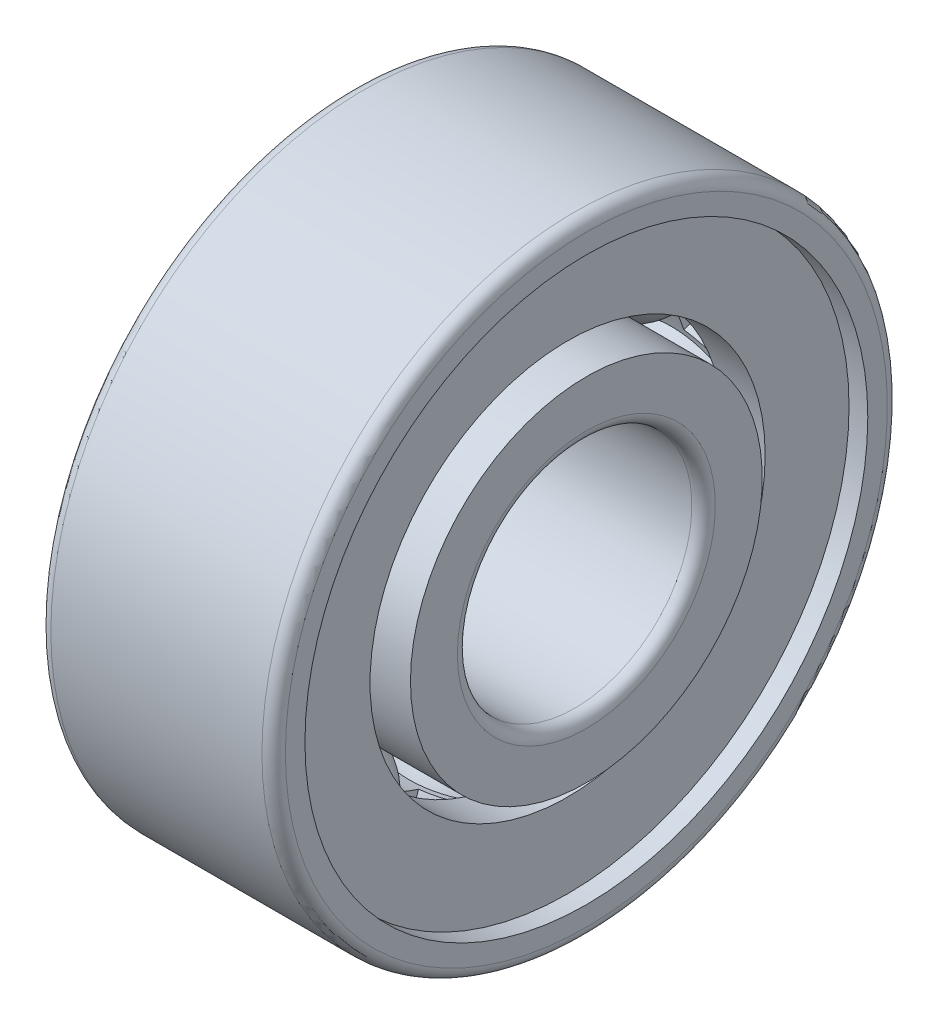
SolidWorks part; units mm, degrees
revolve "凸台-旋转2" add sketch "草图6" angle 360 about L4
sketch "草图6" plane through (0, 0, 0) normal (0, 0, 1) x (1, 0, 0)
  line L0 (0, 0) -> (5.5439, 0) construction
  line L1 (-12.4206, 0) -> (9.8128, 0) construction
  line L2 (0, 0) -> (0, 11.4011) construction
  line L3 (-5.5681, 2.925) -> (6.1049, 2.925) construction
  line L4 (-5.5681, 2.925) -> (6.1049, 2.925) construction
  line L5 (-0.84, 2.925) -> (0.84, 2.925)
  arc A0 (-0.84, 2.925) -> (0.84, 2.925) centre (0, 2.925) ccw
  dimension "Dw" = 1.68
revolve "基体-旋转" add sketch "草图2" angle 360 about L0
sketch "草图2" plane through (0, 0, 0) normal (0, 0, 1) x (1, 0, 0)
  line L0 (-12.4206, 0) -> (9.8128, 0) construction
  line L1 (0, 0) -> (0, 37.3563) construction
  line L2 (-5.5681, 2.925) -> (6.1049, 2.925) construction
  line L3 (-0.1848, 3.156) -> (0.1848, 3.156)
  line L4 (-0.1848, 3.156) -> (-0.1848, 2.694)
  line L5 (-0.1848, 2.694) -> (0.1848, 2.694)
  line L6 (0.1848, 3.156) -> (0.1848, 2.694)
  dimension "D1" = 0.3696
  dimension "D2" = 0.1848
  dimension "D3" = 0.462
  dimension "D4" = 0.231
  dimension "D5" = 2.925
revolve "凸台-旋转1" add sketch "草图3" angle 360 about L1
sketch "草图3" plane through (0, 0, 0) normal (0, 0, 1) x (1, 0, 0)
  line L0 (-5.5681, 2.925) -> (6.1049, 2.925) construction
  line L1 (-5.5681, 2.925) -> (6.1049, 2.925) construction
  line L2 (-12.4206, 0) -> (9.8128, 0) construction
  line L3 (-12.4206, 0) -> (9.8128, 0) construction
  line L4 (0, 0) -> (0, 37.3563) construction
  line L5 (0, 0) -> (0, 37.3563) construction
  line L6 (-0.924, 2.925) -> (0.924, 2.925)
  arc A0 (-0.924, 2.925) -> (0.924, 2.925) centre (0, 2.925) ccw
  dimension "Dwww" = 1.848
  dimension "D2" = 0.924
pattern_circular "阵列(圆周)1" count 8 over 360 about axis through (-12.4206, 0, 0) along (1, 0, 0) of "凸台-旋转1"
revolve "凸台-旋转3" add sketch "草图7" angle 360 about L0
sketch "草图7" plane through (0, 0, 0) normal (0, 0, 1) x (1, 0, 0)
  line L0 (0, 0) -> (6.6488, 0) construction
  line L1 (0, 0) -> (0, 16.8954) construction
  line L2 (-1.35, 4) -> (1.35, 4)
  line L3 (-1.5, 3.85) -> (-1.5, 3.6)
  line L4 (-1.5, 3.6) -> (-0.483, 3.6)
  line L5 (1.5, 3.85) -> (1.5, 3.6)
  line L6 (0.483, 3.6) -> (0.7248, 3.6)
  line L7 (1.26, 3.6) -> (1.5, 3.6)
  line L8 (0.7248, 3.4) -> (1.26, 3.4)
  line L9 (0.7248, 3.4) -> (0.7248, 3.6)
  line L11 (1.26, 3.4) -> (1.26, 3.6)
  arc A0 (-1.35, 4) -> (-1.5, 3.85) centre (-1.35, 3.85) ccw
  arc A1 (1.35, 4) -> (1.5, 3.85) centre (1.35, 3.85) cw
  arc A2 (0.8076, 3.156) -> (-0.8076, 3.156) centre (0, 2.925) ccw construction
  arc A3 (0.5, 3.6) -> (0, 3.765) centre (0, 2.925) ccw construction
  arc A4 (0.483, 3.6) -> (-0.483, 3.6) centre (0, 2.925) ccw
  point P10 (-1.5, 4)
  point P13 (1.5, 4)
  dimension "D3" = 1.5
  dimension "D4" = 0.5352
  dimension "D5" = 6.8
  dimension "D6" = 0.24
  dimension "B" = 3
ref_plane "基准面1" through (0, 0, 0) normal (0, 0, 1) x (1, 0, 0)
ref_plane "基准面2" through (0, 0, 0) normal (0, 1, 0) x (1, 0, 0)
ref_plane "基准面3" through (0, 0, 0) normal (1, 0, 0) x (0, 0, -1)
sketch "尺寸草图" plane through (0, 0, 0) normal (0, 0, 1) x (1, 0, 0)
  point P0 (0, -75.4307)
  point P1 (1.68, -75.4307)
  point P2 (0, 50.7088)
  point P3 (3, 50.7088)
  point P4 (8, 50.7088)
  point P5 (3, 50.7088)
  point P6 (0, -10.9899)
  point P7 (4.5, -10.9899)
  point P8 (6.8, -10.9899)
  point P9 (0.15, -10.9899)
  point P10 (8, -75.4307)
  dimension "B" = 3
sketch "草图4" plane through (0, 0, 0) normal (0, 0, 1) x (1, 0, 0)
  line L0 (0, 0) -> (8.1272, 0) construction
  line L1 (-12.4206, 0) -> (9.8128, 0) construction
  line L3 (-0.1848, 3.156) -> (0.1848, 3.156) construction
  line L4 (-0.924, 4.08) -> (0.924, 4.08)
  line L5 (-0.924, 4.08) -> (-0.924, 3.156)
  line L6 (-0.924, 3.156) -> (0.924, 3.156)
  line L7 (0.924, 4.08) -> (0.924, 3.156)
revolve "切除-旋转1" cut sketch "草图4" angle 360 about L0
sketch "草图5" plane through (0, 0, 0) normal (0, 0, 1) x (1, 0, 0)
  line L0 (0, 0) -> (8.2665, 0) construction
  line L1 (-12.4206, 0) -> (9.8128, 0) construction
  line L2 (-0.1848, 2.694) -> (0.1848, 2.694) construction
  line L3 (-0.924, 2.694) -> (0.924, 2.694)
  line L4 (-0.924, 2.694) -> (-0.924, 1.77)
  line L5 (-0.924, 1.77) -> (0.924, 1.77)
  line L6 (0.924, 2.694) -> (0.924, 1.77)
revolve "切除-旋转2" cut sketch "草图5" angle 360 about L0
pattern_circular "阵列(圆周)2" count 8 over 360 about axis through (-12.4206, 0, 0) along (1, 0, 0) of "凸台-旋转2"
sketch "草图8" plane through (0, 0, 0) normal (0, 0, 1) x (1, 0, 0)
  line L0 (-12.4206, 0) -> (9.8128, 0) construction
  line L1 (-12.4206, 0) -> (9.8128, 0) construction
  line L2 (1.5, 3.85) -> (1.5, 3.6) construction
  line L3 (-1.5, 2.25) -> (-0.483, 2.25)
  line L4 (-1.5, 2.25) -> (-1.5, 1.65)
  line L5 (-1.35, 1.5) -> (1.35, 1.5)
  line L6 (1.5, 2.25) -> (1.5, 1.65)
  line L7 (-1.5, 3.85) -> (-1.5, 3.6) construction
  line L8 (0.483, 2.25) -> (1.5, 2.25)
  arc A0 (-1.5, 1.65) -> (-1.35, 1.5) centre (-1.35, 1.65) ccw
  arc A1 (1.35, 1.5) -> (1.5, 1.65) centre (1.35, 1.65) ccw
  arc A2 (-0.8076, 2.694) -> (0.8076, 2.694) centre (0, 2.925) ccw construction
  arc A3 (-0.8076, 2.694) -> (0.8076, 2.694) centre (0, 2.925) ccw construction
  arc A4 (-0.483, 2.25) -> (0.483, 2.25) centre (0, 2.925) ccw
  dimension "D1" = 0.15
  dimension "DD" = 3
  dimension "D2" = 0.01
revolve "凸台-旋转4" add sketch "草图8" angle 360 about L1
sketch "草图10" plane through (0, 0, 0) normal (0, 0, 1) x (1, 0, 0)
  line L0 (0.7248, 3.6) -> (0.7248, -3.6) construction
  line L1 (1.26, 3.4) -> (0.7248, 3.4)
  line L2 (1.26, 3.4) -> (1.26, 2.5272)
  line L3 (1.26, 2.5272) -> (0.7248, 2.5272)
  line L4 (0.7248, 3.4) -> (0.7248, 2.5272)
  line L5 (0.483, 2.25) -> (1.5, 2.25) construction
  line L6 (0, 0) -> (-5.3515, 0) construction
  line L7 (-12.4206, 0) -> (9.8128, 0) construction
  dimension "D1" = 0.2772
revolve "凸台-旋转5" add sketch "草图10" angle 360 about L6
sketch "草图11" plane through (0, 0, 0) normal (1, 0, 0) x (0, 0, -1)
  circle A0 centre (0, 0) radius 4
  circle A1 centre (0, 0) radius 4 construction
extrude "切除-拉伸1" cut sketch "草图11" against normal blind 10
mirror "镜向所有1" about plane through (0, 0, 0) normal (1, 0, 0) of bodies 109
equation "\"D5@草图7\" = \"防尘圈径D3@尺寸草图\""
equation "\"Z@阵列(圆周)1\"=\"球数Z@尺寸草图\" "
equation "\"Dw@草图6\"=\"球径DW@尺寸草图\""
equation "\"DD@草图8\"=\"d@尺寸草图\""
equation "\"D@草图7\"=\"DD@尺寸草图\""
equation "\"B@草图7\"=\"B@尺寸草图\" "
equation "\"DD2@草图8\"=\"内圈外径DD2@尺寸草图\""
equation "\"R@草图7\"=\"r@尺寸草图\""
equation "\"D3@草图2\" = 0.25*\"Dwww@草图3\""
equation "\"D4@草图2\" = \"D3@草图2\"/2"
equation "\"Dwww@草图3\" = 1.1*\"Dw@草图6\""
equation "\"D2@草图3\" = 0.5*\"Dwww@草图3\""
equation "\"D1@草图2\" = 0.2*\"Dwww@草图3\""
equation "\"D2@草图2\" = 0.5*\"D1@草图2\""
equation "\"切除位置@草图4\" = \"Dwww@草图3\"/2"
equation "\"D1@阵列(圆周)2\" = \"Z@阵列(圆周)1\""
equation "\"D3@草图7\" = \"B@草图7\" / 2"
equation "\"D1@草图8\" = \"R@草图7\""
equation "\"D2@草图7\" = 0.9*\"D@草图7\""
equation "\"D5@草图2\" = 0.25* ( \"D2@草图7\" + \"DD2@草图8\" )  "
equation "\"D6@草图7\" = 0.08 * \"B@草图7\""
equation "\"D1@草图10\" = 0.15*\"Dwww@草图3\""
